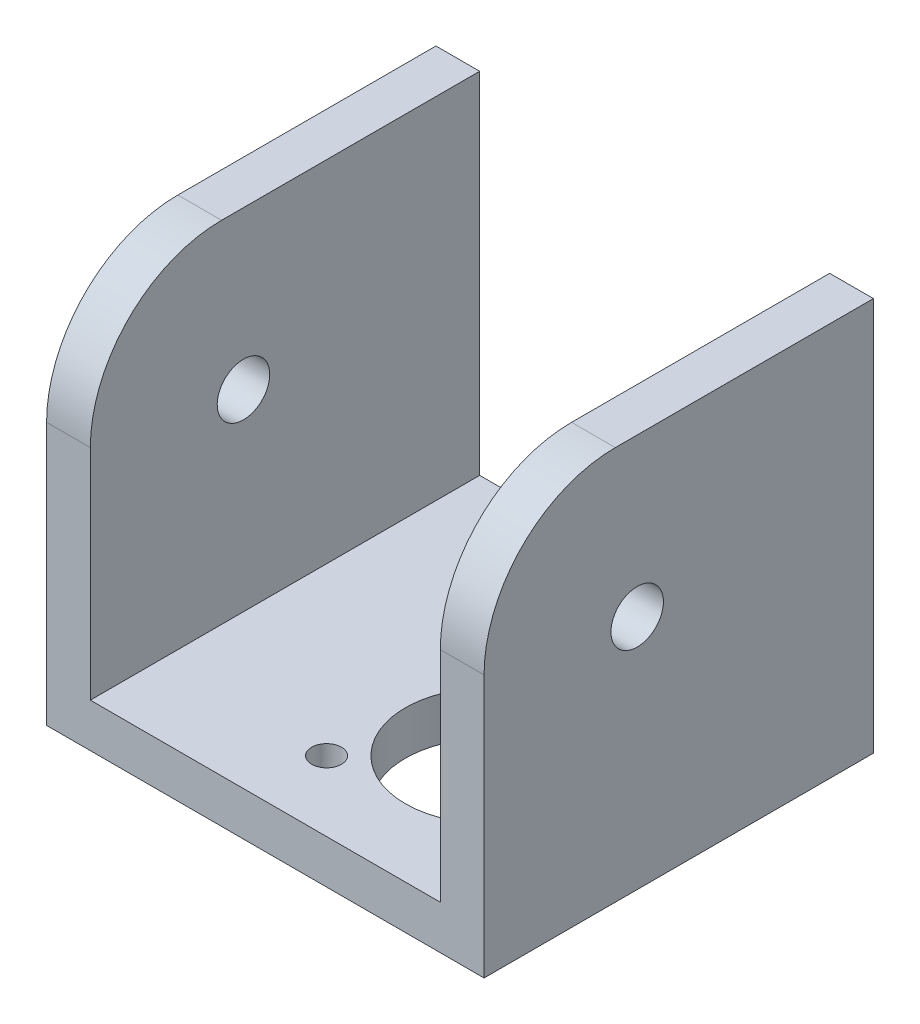
SolidWorks part; units mm, degrees
ref_plane "Plan de face" through (0, 0, 0) normal (0, 0, 1) x (1, 0, 0)
ref_plane "Plan de dessus" through (0, 0, 0) normal (0, 1, 0) x (1, 0, 0)
ref_plane "Plan de droite" through (0, 0, 0) normal (1, 0, 0) x (0, 0, -1)
sketch "Esquisse1" plane through (0, 0, 0) normal (0, 0, 1) x (1, 0, 0)
  line L1 (0, 0) -> (50, 0)
  line L2 (0, 0) -> (0, 45)
  line L3 (0, 45) -> (50, 45)
  line L4 (50, 0) -> (50, 45)
  dimension "D1" = 50
  dimension "D2" = 45
extrude "Boss.-Extru.1" add sketch "Esquisse1" along normal blind 44.5
sketch "Esquisse2" plane through (0, 0, 44.5) normal (0, 0, 1) x (1, 0, 0)
  line L4 (50, 45) -> (0, 45) construction
  line L5 (45, 45) -> (5, 45)
  line L8 (5, 40) -> (5, 5)
  line L9 (5, 5) -> (45, 5)
  line L10 (45, 5) -> (45, 40)
  line L11 (45, 40) -> (5, 40)
  line L12 (5, 45) -> (5, 5)
  line L13 (5, 5) -> (45, 5)
  line L14 (45, 5) -> (45, 45)
  dimension "D1" = 5
extrude "Enlèv. mat.-Extru.1" cut sketch "Esquisse2" against normal up to surface (44.5 mm away) up to face at (25, 22.5, 0)
sketch "Esquisse3" plane through (0, 5, 0) normal (0, 1, 0) x (1, 0, 0)
  line L0 (5, -44.5) -> (45, -44.5) construction
  line L1 (50, -44.5) -> (50, 0) construction
  line L3 (42.5, -18) -> (24, -18) construction
  line L4 (42.5, -18) -> (42.5, -36.5) construction
  line L5 (42.5, -36.5) -> (24, -36.5) construction
  line L6 (24, -18) -> (24, -36.5) construction
  circle A0 centre (33.25, -27.25) radius 9.5
  circle A2 centre (42.5, -18) radius 1.5
  circle A3 centre (24, -18) radius 1.5
  circle A4 centre (24, -36.5) radius 1.5
  circle A5 centre (42.5, -36.5) radius 1.5
  point P14 (33.25, -18)
  point P15 (36.0275, -27.25)
  point P18 (42.5, -27.25)
  dimension "D1" = 19
  dimension "D5" = 3
  dimension "D9" = 3
  dimension "D10" = 3
  dimension "D11" = 3
  dimension "D2" = 17.25
  dimension "D3" = 16.75
  dimension "D7" = 18.5
  dimension "D8" = 18.5
extrude "Enlèv. mat.-Extru.2" cut sketch "Esquisse3" against normal up to surface (5 mm away) up to face at (25, 0, 22.25)
hole_wizard "Dégagement M31" positions "Esquisse4" profile "Esquisse6" hole size "M3" standard "ISO" end condition through all
sketch "Esquisse4" plane through (0, 5, 0) normal (0, 1, 0) x (1, 0, 0)
  point P0 (42.5, -18)
  point P3 (24, -18)
  point P6 (24, -36.5)
  point P9 (42.5, -36.5)
sketch "Esquisse6" plane through (42.5, 5, 18) normal (1, 0, 0) x (0, 0, 1)
  line L0 (0, 0) -> (0, 5)
  line L1 (0, 5) -> (1.7, 5)
  line L2 (1.7, 5) -> (1.7, 0)
  line L5 (1.7, 0) -> (0, 0)
  line L11 (0, -6.35) -> (0, 107.95) construction
  dimension "Diamètre du perçage jusqu'au prochain" = 3.4
  dimension "Profondeur du perçage jusqu'au prochain" = 5
pattern_circular "Répétition circulaire1" [suppressed] count 4 over 360 of bodies 104
fillet "Congé1" radius 15 2 edges at (2.5, 45, 44.5) (47.5, 45, 44.5)
sketch "Esquisse7" plane through (50, 0, 0) normal (1, 0, 0) x (0, 0, -1)
  line L0 (-44.5, 0) -> (0, 0) construction
  line L1 (0, 0) -> (0, 45) construction
  circle A0 centre (-27, 27) radius 3
  dimension "D1" = 6
  dimension "D2" = 27
  dimension "D3" = 27
extrude "Enlèv. mat.-Extru.3" cut sketch "Esquisse7" against normal up to surface (50 mm away) up to face at (0, 24.6213, 24.3213)
equation "\"D8@Esquisse3\"=\"D7@Esquisse3\""
equation "\"D2@Esquisse7\"=24+\"D1@Esquisse7\"/2"
equation "\"D3@Esquisse7\"=\"D2@Esquisse7\""
